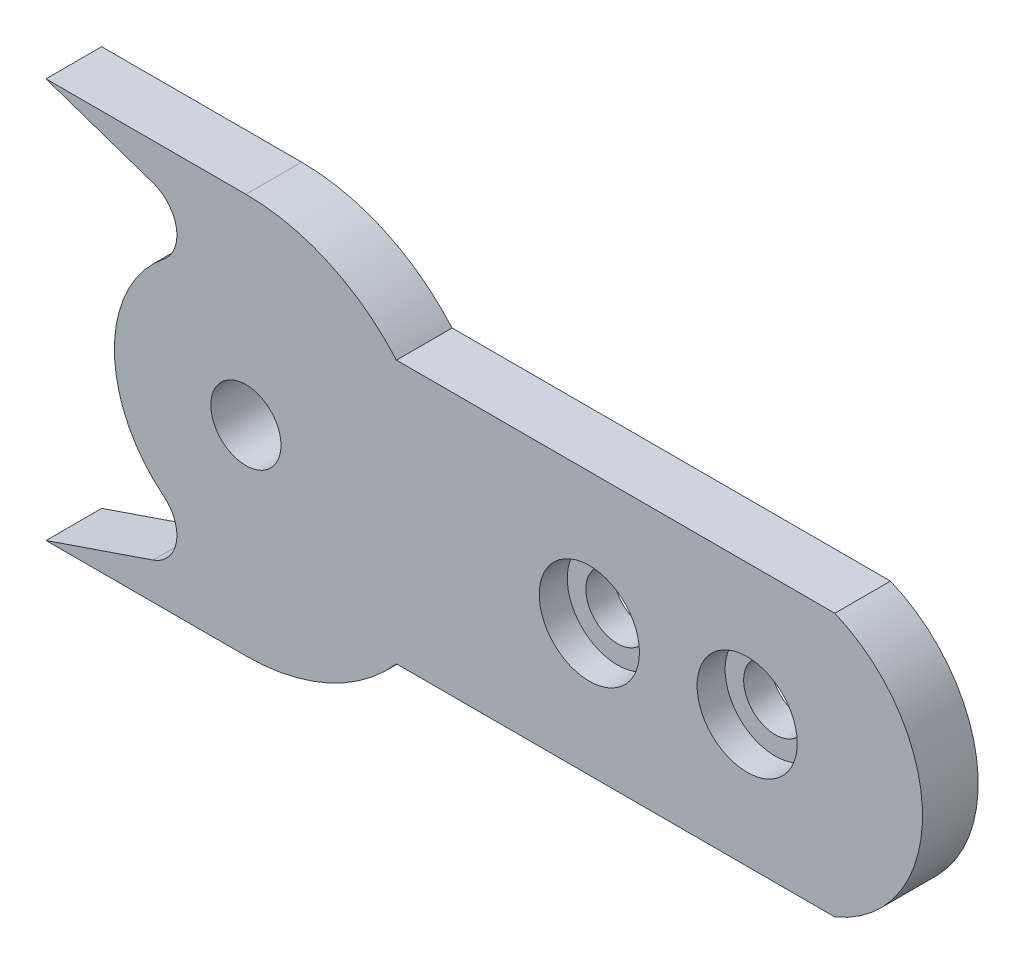
SolidWorks part; units mm, degrees
material "6061-T6 (SS)"
ref_plane "Front Plane" through (0, 0, 0) normal (0, 0, 1) x (1, 0, 0)
ref_plane "Top Plane" through (0, 0, 0) normal (0, 1, 0) x (1, 0, 0)
ref_plane "Right Plane" through (0, 0, 0) normal (1, 0, 0) x (0, 0, -1)
sketch "Sketch1" plane through (0, 0, 0) normal (0, 0, 1) x (1, 0, 0)
  line L0 (0, -45) -> (0, -57) construction
  line L1 (-57, -57) -> (0, -37.5)
  line L2 (-57, -57) -> (0, -57)
  line L3 (-45, 0) -> (-57, 0) construction
  line L4 (-57, 57) -> (0, 57)
  line L5 (-57, 57) -> (0, 37.5)
  line L6 (0, 0) -> (57, 0) construction
  line L7 (42.9273, -37.5) -> (167.9273, -37.5)
  line L8 (42.9273, 37.5) -> (167.9273, 37.5)
  line L9 (167.9273, 37.5) -> (167.9273, -37.5) construction
  circle A0 centre (0, 0) radius 45 construction
  circle A1 centre (0, 0) radius 57 construction
  arc A2 (0, 37.5) -> (0, -37.5) centre (0, 0) ccw
  arc A3 (0, -57) -> (42.9273, -37.5) centre (0, 0) ccw
  arc A4 (0, 57) -> (42.9273, 37.5) centre (0, 0) cw
  circle A5 centre (0, 0) radius 10
  arc A6 (167.9273, 37.5) -> (167.9273, -37.5) centre (152.3023, 0) cw
  point P21 (192.9273, 0)
  dimension "D1" = 90
  dimension "D4" = 75
  dimension "D8" = 20
  dimension "D2" = 12
  dimension "D3" = 12
  dimension "D5" = 75
  dimension "D6" = 18.886
  dimension "D7" = 125
  dimension "D9" = 25
extrude "Boss-Extrude1" add sketch "Sketch1" along normal mid plane 15.875
fillet "Fillet1" radius 10 2 edges at (0, -37.5, 0) (0, 37.5, 0)
sketch "Sketch2" plane through (0, 0, 7.9375) normal (0, 0, 1) x (1, 0, 0)
  circle A0 centre (142.9273, 0) radius 14.2875
  circle A1 centre (97.9273, 0) radius 14.2875
  dimension "D2" = 28.575
  dimension "D1" = 25
  dimension "D3" = 45
extrude "Cut-Extrude1" cut sketch "Sketch2" against normal blind 8
sketch "Sketch3" plane through (0, 0, 7.9375) normal (0, 0, 1) x (1, 0, 0)
  circle A1 centre (142.9273, 0) radius 14.2875 construction
  circle A2 centre (97.9273, 0) radius 9
  circle A3 centre (142.9273, 0) radius 9
  dimension "D1" = 18
extrude "Cut-Extrude2" cut sketch "Sketch3" against normal through all
equation "\"D1@Boss-Extrude1\"=0.625in"
equation "\"D2@Sketch2\"=1.125in"
